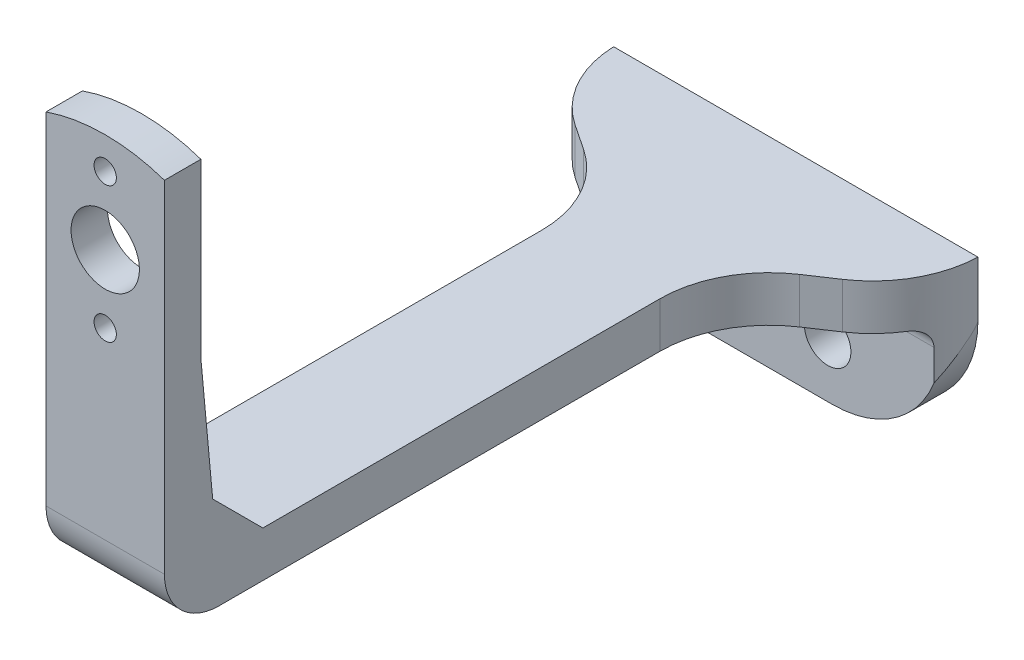
SolidWorks part; units mm, degrees
ref_plane "Alzado" through (0, 0, 0) normal (0, 0, 1) x (1, 0, 0)
ref_plane "Planta" through (0, 0, 0) normal (0, 1, 0) x (1, 0, 0)
ref_plane "Vista lateral" through (0, 0, 0) normal (1, 0, 0) x (0, 0, -1)
sketch "Croquis2" plane through (0, 0, 0) normal (0, 0, 1) x (1, 0, 0)
  line L0 (-7.5, 0) -> (7.5, 0) construction
  line L1 (0, 0) -> (0, 40.6) construction
  line L2 (0, 0) -> (0, -6) construction
  line L4 (0, 33.1578) -> (0, 48.0422) construction
  line L5 (-6.115, 40.6) -> (6.115, 40.6) construction
  line L6 (-20, 31.5422) -> (-20, -6)
  line L7 (-20, -6) -> (20, -6)
  line L8 (20, 31.5422) -> (20, -6)
  circle A0 centre (-7.5, 0) radius 2.55
  circle A1 centre (7.5, 0) radius 2.55
  circle A2 centre (0, 40.6) radius 3.75
  circle A3 centre (0, 40.6) radius 6.115 construction
  circle A4 centre (0, 48.0422) radius 1.225
  circle A5 centre (0, 33.1578) radius 1.225
  arc A6 (20, 31.5422) -> (0, 51.5422) centre (0, 31.5422) ccw
  arc A7 (0, 51.5422) -> (-20, 31.5422) centre (0, 31.5422) ccw
  point P4 (0, 0)
  point P17 (-35.5895, 65.5486)
  point P21 (0, -6)
  point P26 (-36.1596, 62.3537)
  point P32 (0, 40.6)
  dimension "D1" = 15
  dimension "D2" = 5.1
  dimension "D3" = 5.1
  dimension "D5" = 7.5
  dimension "D6" = 12.23
  dimension "D7" = 2.45
  dimension "D8" = 2.45
  dimension "D11" = 20
  dimension "D12" = 20
  dimension "D4" = 40.6
  dimension "D9" = 14.8844
  dimension "D10" = 6
  dimension "D13" = 40
extrude "Saliente-Extruir1" add sketch "Croquis2" along normal blind 75.8075
sketch "Croquis4" plane through (-20, 0, 0) normal (-1, 0, 0) x (0, 0, 1)
  line L0 (0, 12) -> (70, 12)
  line L1 (0, 31.5422) -> (0, -6) construction
  line L2 (70, 12) -> (71.8075, 31.5422)
  line L3 (75.8075, 31.5422) -> (0, 31.5422) construction
  line L4 (71.8075, 31.5422) -> (71.8075, 53.7131)
  line L5 (71.8075, 53.7131) -> (0, 53.7131)
  line L6 (0, 53.7131) -> (0, 12)
  line L7 (75.8075, -6) -> (0, -6) construction
  line L8 (75.8075, 31.5422) -> (75.8075, 51.5422) construction
  dimension "D1" = 18
  dimension "D2" = 70
  dimension "D3" = 4
extrude "Cortar-Extruir1" cut sketch "Croquis4" against normal through all
sketch "Croquis5" plane through (-20, 0, 0) normal (-1, 0, 0) x (0, 0, 1)
  line L0 (75.8075, -6) -> (0, -6) construction
  line L1 (4, -6) -> (75.8075, -6)
  line L2 (4, -6) -> (4, 7)
  line L3 (4, 7) -> (75.8075, 7)
  line L4 (75.8075, -6) -> (75.8075, 7)
  line L5 (75.8075, 31.5422) -> (75.8075, -6) construction
  line L6 (0, 12) -> (0, -6) construction
  dimension "D1" = 13
  dimension "D2" = 4
extrude "Cortar-Extruir2" cut sketch "Croquis5" against normal through all
sketch "Croquis6" plane through (0, 0, 4) normal (0, 0, 1) x (1, 0, 0)
  circle A0 centre (-7.5, 0) radius 4
  dimension "D1" = 8
fillet "Redondeo1" radius 2 1 edges at (0, 7, 4)
chamfer "Chaflán1" distance 5 angle 45 1 edges at (0, 12, 70) first distance on face at (0, 12, 35)
fillet "Redondeo2" radius 12 2 edges at (20, -6, 2) (-20, -6, 2)
sketch "Croquis7" plane through (0, 7, 0) normal (0, -1, 0) x (1, 0, 0)
  line L0 (-20, 6) -> (-6.5, 15)
  line L1 (-6.5, 15) -> (-6.5, 75.8075)
  line L2 (20, 75.8075) -> (-20, 75.8075) construction
  line L3 (-6.5, 75.8075) -> (-20, 75.8075)
  line L4 (-20, 75.8075) -> (-20, 6)
  line L5 (0, 75.8075) -> (0, 6) construction
  line L6 (-20, 6) -> (20, 6) construction
  line L7 (20, 75.8075) -> (20, 6)
  line L8 (6.5, 75.8075) -> (20, 75.8075)
  line L9 (6.5, 15) -> (6.5, 75.8075)
  line L10 (20, 6) -> (6.5, 15)
  dimension "D1" = 13.5
  dimension "D2" = 9
extrude "Cortar-Extruir3" cut sketch "Croquis7" against normal through all
fillet "Redondeo3" radius 12 4 edges at (20, 9.5, 6) (-20, 9.5, 6) (-6.5, 9.5, 15) (6.5, 9.5, 15)
fillet "Redondeo4" radius 6 1 edges at (0, 7, 75.8075)
